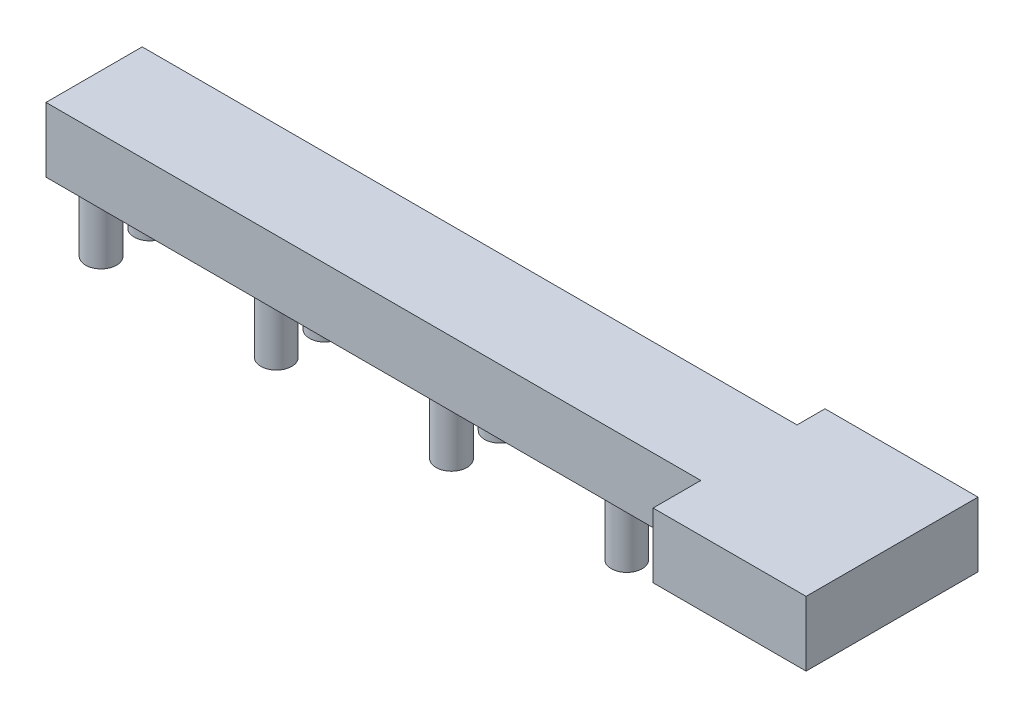
SolidWorks part; units mm, degrees
ref_plane "前视基准面" through (0, 0, 0) normal (0, 0, 1) x (1, 0, 0)
ref_plane "上视基准面" through (0, 0, 0) normal (0, 1, 0) x (1, 0, 0)
ref_plane "右视基准面" through (0, 0, 0) normal (1, 0, 0) x (0, 0, -1)
sketch "草图1" plane through (0, 0, 0) normal (0, 1, 0) x (1, 0, 0)
  line L0 (-88.7037, 0) -> (-88.7037, 7.5)
  line L1 (-88.7037, 7.5) -> (-83.8737, 7.5)
  line L2 (-83.8737, 7.5) -> (-56.8237, 7.5)
  line L3 (-56.8237, 7.5) -> (-29.7737, 7.5)
  line L4 (-29.7737, 7.5) -> (-2.7237, 7.5)
  line L5 (-2.7237, 7.5) -> (12.3863, 7.5)
  line L6 (12.3863, 7.5) -> (12.3863, 11.82)
  line L7 (12.3863, 11.82) -> (36.0063, 11.82)
  line L8 (36.0063, 11.82) -> (36.0063, -14.72)
  line L9 (36.0063, -14.72) -> (12.3863, -14.72)
  line L10 (12.3863, -14.72) -> (12.3863, -7.35)
  line L11 (12.3863, -7.35) -> (-88.7037, -7.35)
  line L12 (-88.7037, -7.35) -> (-88.7037, 0)
  dimension "D1" = 15.11
  dimension "D2" = 27.05
  dimension "D3" = 23.62
  dimension "D4" = 26.54
  dimension "D5" = 23.62
  dimension "D6" = 4.83
  dimension "D7" = 27.05
  dimension "D8" = 27.05
extrude "凸台-拉伸1" add sketch "草图1" along normal blind 10
sketch "草图3" plane through (0, 0, 0) normal (0, -1, 0) x (1, 0, 0)
  circle A0 centre (-83.8737, 3.675) radius 2.3929
  circle A1 centre (-83.8737, -3.825) radius 2.39
extrude "凸台-拉伸2" add sketch "草图3" along normal blind 10
ref_axis "基准轴1" through (12.3863, 10, -7.5) along (-1, 0, 0)
pattern_linear "阵列(线性)1" count 4 spacing 27.05 along (1, 0, 0) of "凸台-拉伸2"
